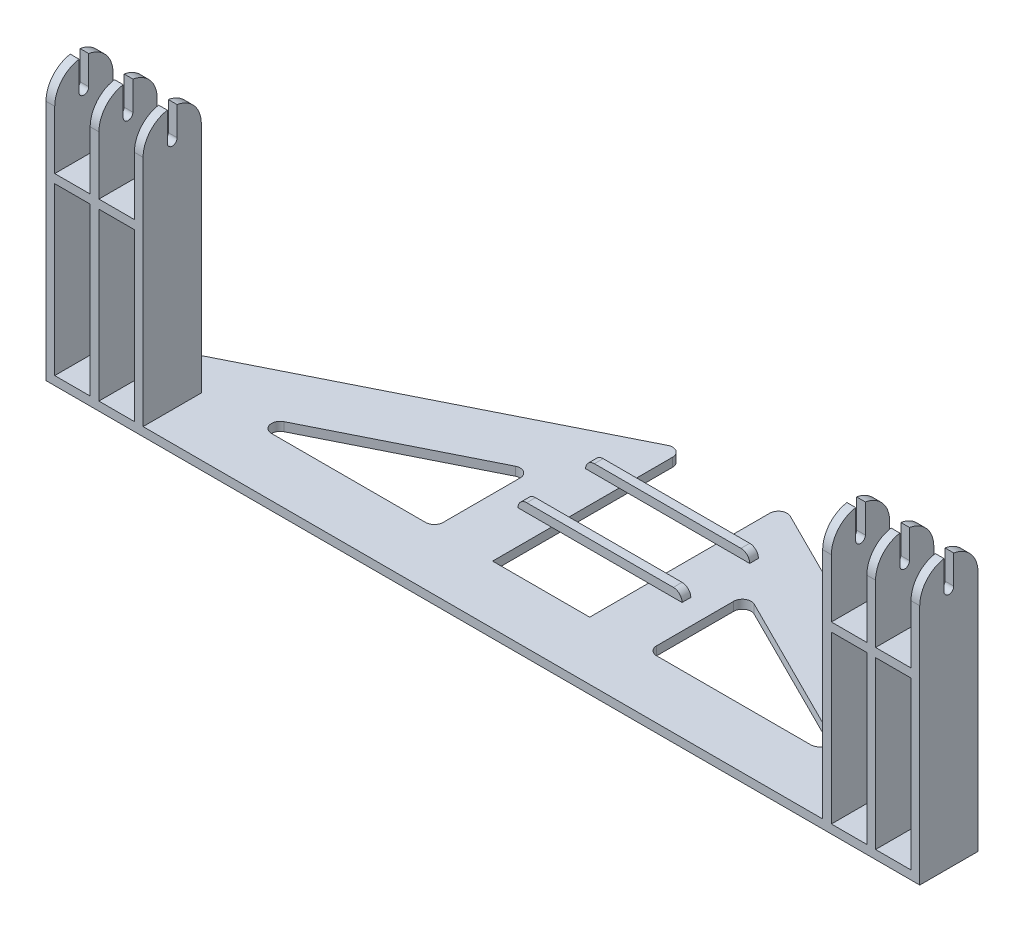
SolidWorks part; units mm, degrees
ref_plane "Front Plane" through (0, 0, 0) normal (0, 0, 1) x (1, 0, 0)
ref_plane "Top Plane" through (0, 0, 0) normal (0, 1, 0) x (1, 0, 0)
ref_plane "Right Plane" through (0, 0, 0) normal (1, 0, 0) x (0, 0, -1)
sketch "Sketch1" plane through (0, 0, 0) normal (0, 0, 1) x (1, 0, 0)
  line L0 (-450, 600) -> (-450, 0)
  line L1 (-450, 0) -> (450, 0)
  line L2 (450, 0) -> (450, 600)
  line L3 (450, 600) -> (350, 600)
  line L4 (350, 600) -> (350, 9)
  line L5 (350, 9) -> (-350, 9)
  line L6 (-350, 9) -> (-350, 600)
  line L7 (-350, 600) -> (-450, 600)
  line L8 (-350, 600) -> (350, 600) construction
  line L9 (0, 0) -> (0, 9) construction
  point P8 (0, 0)
  point P10 (-224.3794, 293.9621)
  point P13 (724.7095, 600)
  point P14 (600.3374, 600)
  dimension "D1" = 9
  dimension "D2" = 600
  dimension "D3" = 100
  dimension "D4" = 700
extrude "Boss-Extrude1" add sketch "Sketch1" along normal blind 50 and the other way blind 50
sketch "Sketch2" plane through (0, 0, 0) normal (1, 0, 0) x (0, 0, -1)
  line L0 (0, 249.2) -> (0, 20) construction
  line L1 (0, 20) -> (0, 0) construction
  line L2 (5, 249.2) -> (5, 278.7804)
  line L3 (-5, 249.2) -> (-5, 278.7804)
  line L4 (30, 249.2) -> (30, 0)
  line L5 (50, 600) -> (-50, 600)
  line L6 (50, 600) -> (50, 0)
  line L7 (50, 0) -> (-50, 0)
  line L8 (-50, 600) -> (-50, 0)
  line L9 (-30, 249.2) -> (-30, 0)
  circle A0 centre (0, 249.2) radius 229.2 construction
  circle A1 centre (0, 249.2) radius 5
  circle A2 centre (0, 249.2) radius 30
  dimension "D1" = 458.4
  dimension "D3" = 10
  dimension "D4" = 25
  dimension "D2" = 20
extrude "Cut-Extrude1" cut sketch "Sketch2" against normal through all both and the other way through all contours A2 L4 L7 L6 L5 L8 L9 | L2 A2 L3 A1 | A1 region at (0, 266.07, 0) region at (0, 361.337, 0)
sketch "Sketch3" plane through (0, 0, 0) normal (0, 0, 1) x (1, 0, 0)
  line L0 (-441, 9) -> (-359, 9)
  line L1 (-450, 278.7804) -> (-441, 278.7804)
  line L2 (-450, 278.7804) -> (-450, 9)
  line L3 (-450, 9) -> (-441, 9)
  line L4 (-441, 278.7804) -> (-441, 9)
  line L5 (-350, 278.7804) -> (-359, 278.7804)
  line L6 (-350, 278.7804) -> (-350, 9)
  line L7 (-350, 9) -> (-359, 9)
  line L8 (-359, 278.7804) -> (-359, 9)
  line L9 (350, 278.7804) -> (359, 278.7804)
  line L10 (350, 278.7804) -> (350, 9)
  line L11 (350, 9) -> (359, 9)
  line L12 (359, 278.7804) -> (359, 9)
  line L13 (450, 278.7804) -> (441, 278.7804)
  line L14 (450, 278.7804) -> (450, 9)
  line L15 (450, 9) -> (441, 9)
  line L16 (441, 278.7804) -> (441, 9)
  line L17 (441, 9) -> (359, 9)
  line L18 (350, 9) -> (-350, 9) construction
  line L19 (-350, 9) -> (350, 9) construction
  line L20 (-441, 278.7804) -> (-359, 278.7804)
  line L21 (359, 278.7804) -> (441, 278.7804)
  line L22 (-400, 278.7804) -> (-400, 9) construction
  line L23 (-404.5, 9) -> (-395.5, 9)
  line L24 (-404.5, 9) -> (-404.5, 278.7804)
  line L25 (-404.5, 278.7804) -> (-395.5, 278.7804)
  line L26 (-395.5, 9) -> (-395.5, 278.7804)
  line L27 (-450, 0) -> (450, 0) construction
  line L28 (395.5, 0) -> (404.5, 0)
  line L29 (395.5, 0) -> (395.5, 278.7804)
  line L30 (395.5, 278.7804) -> (404.5, 278.7804)
  line L31 (404.5, 0) -> (404.5, 278.7804)
  line L32 (400, 9) -> (400, 278.7804) construction
  dimension "D1" = 9
  dimension "D2" = 9
  dimension "D3" = 9
extrude "Cut-Extrude3" cut sketch "Sketch3" against normal through all both and the other way through all contours L0 L24 L20 L4 | L26 L0 L8 L20 | L17 L29 L21 L12 | L31 L17 L16 L21 region at (-422.75, 143.8902, 0) region at (-377.25, 143.8902, 0) region at (377.25, 143.8902, 0) region at (422.75, 143.8902, 0)
sketch "Sketch4" plane through (0, 0, 0) normal (0, 1, 0) x (1, 0, 0)
  line L0 (450, 30) -> (50, 230)
  line L1 (50, 230) -> (50, 30)
  line L2 (50, 30) -> (-50, 30)
  line L3 (-50, 30) -> (-50, 230)
  line L4 (-50, 230) -> (-450, 30)
  line L5 (0, 0) -> (0, 30) construction
  line L6 (50, 230) -> (-50, 230) construction
  line L7 (0, 230) -> (0, 30) construction
  line L8 (-350, 30) -> (350, 30) construction
  line L9 (315.8359, 30) -> (110, 132.918)
  line L10 (110, 132.918) -> (110, 30)
  line L11 (110, 30) -> (315.8359, 30)
  line L12 (-110, 132.918) -> (-110, 30)
  line L13 (-315.8359, 30) -> (-110, 132.918)
  line L14 (-110, 30) -> (-315.8359, 30)
  line L15 (450, 30) -> (-450, 30)
  dimension "D1" = 100
  dimension "D2" = 200
  dimension "D3" = 60
  dimension "D4" = 60
extrude "Boss-Extrude2" add sketch "Sketch4" along normal blind 9 contours L15 L3 L4 L13 L12 | L15 L0 L1 L10 L9 region at (185.0339, 0, -108.3223) region at (-185.0339, 0, -108.3223)
sketch "Sketch5" plane through (0, 0, -30) normal (0, 0, -1) x (-1, 0, 0)
  line L0 (450, 249.2) -> (450, 9) construction
  line L1 (450, 189.2) -> (-450, 189.2)
  line L2 (450, 189.2) -> (450, 180.2)
  line L3 (450, 180.2) -> (-450, 180.2)
  line L4 (-450, 189.2) -> (-450, 180.2)
  line L5 (-450, 249.2) -> (-450, 9) construction
  line L6 (350, 180.2) -> (350, 189.2)
  line L7 (350, 249.2) -> (350, 9) construction
  line L8 (-350, 180.2) -> (-350, 189.2)
  line L9 (-350, 9) -> (-350, 249.2) construction
  line L10 (-441, 249.2) -> (-450, 249.2) construction
  point P18 (-445.5, 249.2)
  point P19 (-350, 180.2)
  line M9 (359, 9) -> (359, 249.2)
  dimension "D1" = 9
  dimension "D2" = 60
extrude "Boss-Extrude3" add sketch "Sketch5" against normal up to surface (60 mm away) contours L3 L2 L1 M9 | L3 L8 L1 L4 region at (400, 184.7, -30) region at (-404.5, 184.7, -30) up to face at (0, 128.35, 30)
sketch "Sketch6" plane through (0, 9, 0) normal (0, 1, 0) x (1, 0, 0)
  line L0 (84.5, 99.6667) -> (84.5, 160.3333) construction
  line L1 (84.5, 169.3333) -> (-84.5, 169.3333)
  line L2 (84.5, 169.3333) -> (84.5, 160.3333)
  line L3 (84.5, 160.3333) -> (-84.5, 160.3333)
  line L4 (-84.5, 169.3333) -> (-84.5, 160.3333)
  line L5 (84.5, 90.6667) -> (-84.5, 90.6667)
  line L6 (84.5, 90.6667) -> (84.5, 99.6667)
  line L7 (84.5, 99.6667) -> (-84.5, 99.6667)
  line L8 (-84.5, 90.6667) -> (-84.5, 99.6667)
  line L9 (0, 30) -> (0, 90.6667) construction
  line L10 (-50, 30) -> (50, 30) construction
  line L11 (0, 90.6667) -> (0, 99.6667) construction
  line L12 (0, 99.6667) -> (0, 160.3333) construction
  line L13 (0, 160.3333) -> (0, 169.3333) construction
  line L14 (0, 169.3333) -> (0, 230) construction
  line L15 (50, 230) -> (-50, 230) construction
  line L16 (110, 30) -> (84.5, 30) construction
  line L17 (84.5, 30) -> (75.5, 30) construction
  line L18 (75.5, 30) -> (50, 30) construction
  line L19 (84.5, 90.6667) -> (84.5, 30) construction
  dimension "D1" = 9
  dimension "D4" = 9
extrude "Boss-Extrude4" add sketch "Sketch6" along normal blind 9
fillet "Fillet1" radius 9 12 edges at (-315.8359, 4.5, -30) (-110, 4.5, -30) (-110, 4.5, -132.918) (110, 4.5, -132.918) (110, 4.5, -30) (315.8359, 4.5, -30) (-50, 4.5, -230) (50, 4.5, -230) (84.5, 18, -164.8333) (84.5, 18, -95.1667) (-84.5, 18, -95.1667) (-84.5, 18, -164.8333)
